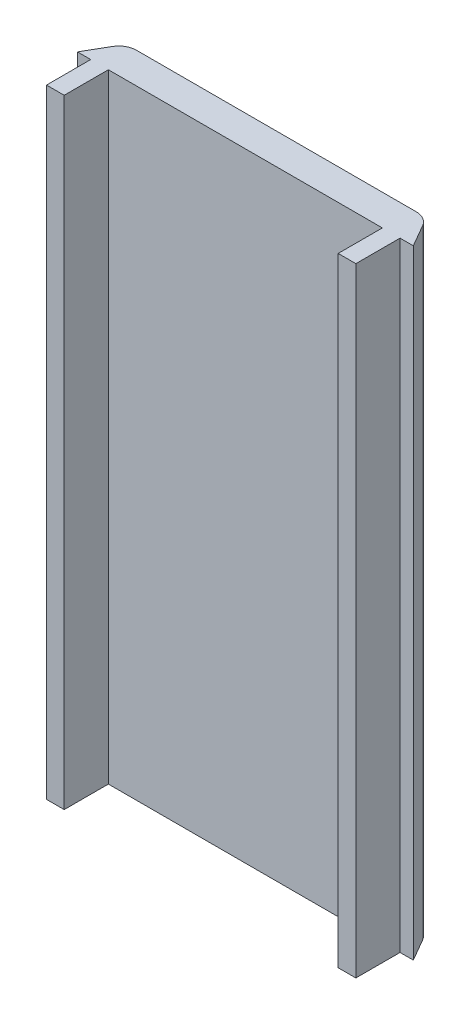
SolidWorks part; units mm, degrees
ref_plane "Front Plane" through (0, 0, 0) normal (0, 0, 1) x (1, 0, 0)
ref_plane "Top Plane" through (0, 0, 0) normal (0, 1, 0) x (1, 0, 0)
ref_plane "Right Plane" through (0, 0, 0) normal (1, 0, 0) x (0, 0, -1)
sketch "Sketch1" plane through (0, 0, 0) normal (0, 1, 0) x (1, 0, 0)
  line L0 (-9.2151, 0) -> (-9.2151, -10)
  line L1 (-9.2151, -10) -> (-5.2151, -10)
  line L2 (-5.2151, -10) -> (-5.2151, 0)
  line L3 (-5.2151, 0) -> (56.7849, 0)
  line L4 (56.7849, 0) -> (56.7849, -10)
  line L5 (56.7849, -10) -> (60.7849, -10)
  line L6 (60.7849, -10) -> (60.7849, 0)
  line L7 (60.7849, 0) -> (63.7849, 0)
  line L8 (-9.2151, 0) -> (-12.2151, 0)
  line L9 (-12.2151, 0) -> (-8.1737, 7)
  line L10 (-8.1737, 7) -> (59.7434, 7)
  line L11 (59.7434, 7) -> (63.7849, 0)
  line L12 (25.7849, 7) -> (25.7849, 0) construction
  dimension "D1" = 3
  dimension "D2" = 10
  dimension "D3" = 70
  dimension "D4" = 7
  dimension "D5" = 4
  dimension "D6" = 60
extrude "Boss-Extrude1" add sketch "Sketch1" along normal blind 140
fillet "Fillet1" radius 4 2 edges at (59.7434, 70, -7) (-8.1737, 70, -7)
